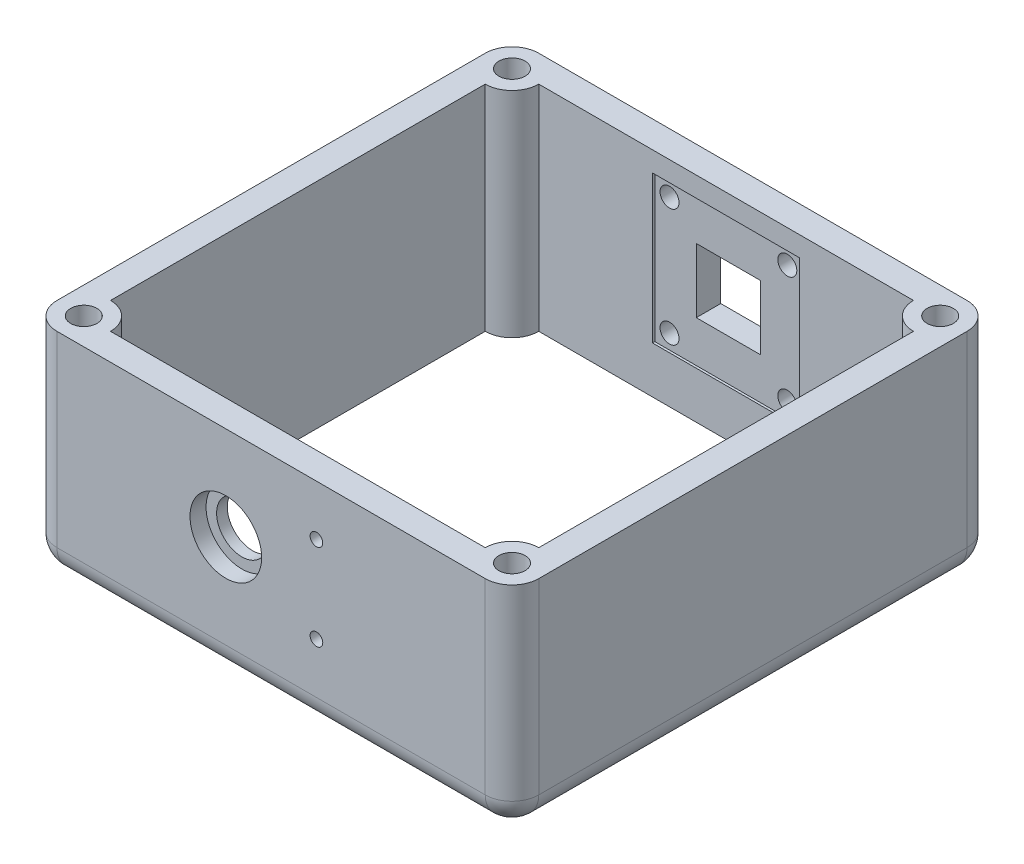
SolidWorks part; units mm, degrees
note: '?' marks a value the reader was unsure of. The reader was unsure of these and kept them because the rebuilt part matched: shared geometry of "Sketch5<3>", "Sketch13<4>", "Sketch13<5>", "Sketch13<6>", "Sketch24<3>".
ref_plane "Front Plane" through (0, 0, 0) normal (0, 0, 1) x (1, 0, 0)
ref_plane "Top Plane" through (0, 0, 0) normal (0, 1, 0) x (1, 0, 0)
ref_plane "Right Plane" through (0, 0, 0) normal (1, 0, 0) x (0, 0, -1)
sketch "Sketch1" plane through (0, 0, 0) normal (0, 1, 0) x (1, 0, 0)
  line L1 (-57.15, 57.15) -> (57.15, 57.15)
  line L2 (-57.15, 57.15) -> (-57.15, -57.15)
  line L3 (-57.15, -57.15) -> (57.15, -57.15)
  line L4 (57.15, 57.15) -> (57.15, -57.15)
  point P4 (0, 57.15)
  point P7 (-57.15, 0)
  dimension "D1" = 114.3
  dimension "D2" = 114.3
extrude "Boss-Extrude1" add sketch "Sketch1" along normal mid plane 50.8
sketch "Sketch2" plane through (0, 25.4, 0) normal (0, 1, 0) x (1, 0, 0)
  line L1 (-50.8, 50.8) -> (50.8, 50.8)
  line L2 (-50.8, 50.8) -> (-50.8, -50.8)
  line L3 (-50.8, -50.8) -> (50.8, -50.8)
  line L4 (50.8, 50.8) -> (50.8, -50.8)
  arc A0 (-50.8, 44.45) -> (-44.45, 50.8) centre (-50.8, 50.8) ccw
  arc A1 (44.45, 50.8) -> (50.8, 44.45) centre (50.8, 50.8) ccw
  arc A2 (-50.8, -44.45) -> (-44.45, -50.8) centre (-50.8, -50.8) cw
  arc A3 (44.45, -50.8) -> (50.8, -44.45) centre (50.8, -50.8) cw
  point P4 (0, 50.8)
  point P5 (50.8, 0)
  dimension "D3" = 6.35
  dimension "D4" = 6.35
  dimension "D5" = 6.35
  dimension "D6" = 6.35
  dimension "D1" = 101.6
  dimension "D2" = 101.6
extrude "Cut-Extrude1" cut sketch "Sketch2" against normal blind 50.8 contours L3 A3 L4 A1 L1 A0 L2 A2
hole_wizard "CBORE for #0 Binding Head Machine Screw1" positions "3DSketch2" profile "Sketch4" counterbore size "#0" standard "ANSI Inch"
sketch3d "3DSketch2"
  point P0 (-50.8, 25.4, -50.8)
  point P3 (50.8, 25.4, -50.8)
  point P6 (-50.8, 25.4, 50.8)
  point P9 (50.8, 25.4, 50.8)
sketch "Sketch4" plane through (-50.8, 25.4, -50.8) normal (1, 0, 0) x (0, 0, 1)
  line L0 (0, 0) -> (0, 18.288)
  line L1 (0, 18.288) -> (0.9271, 17.7309)
  line L2 (0.9271, 17.7309) -> (0.9271, 9.144)
  line L3 (0.9271, 9.144) -> (3.1115, 9.144)
  line L4 (3.1115, 9.144) -> (3.1115, 0)
  line L5 (3.1115, 0) -> (0, 0)
  line L10 (0, 18.288) -> (-0.9271, 17.7309) construction
  line L11 (0, -6.35) -> (0, 107.95) construction
  dimension "Hole Dia." = 1.8542
  dimension "Hole Depth" = 18.288
  dimension "C'Bore Dia." = 6.223
  dimension "C'Bore Depth" = 9.144
  dimension "Drill Angle" = 118
sketch "Sketch5" plane through (0, 0, -50.8) normal (0, 0, 1) x (1, 0, 0)
  line L0 (7.625, 3.175) -> (-7.625, 3.175) construction
  line L1 (-17.47, 20.645) -> (17.47, 20.645)
  line L2 (-17.47, 20.645) -> (-17.47, -14.295)
  line L3 (-17.47, -14.295) -> (17.47, -14.295)
  line L4 (17.47, 20.645) -> (17.47, -14.295)
  line L5 (-7.625, 10.8) -> (7.625, 10.8)
  line L6 (-7.625, 10.8) -> (-7.625, -4.45)
  line L7 (-7.625, -4.45) -> (7.625, -4.45)
  line L8 (7.625, 10.8) -> (7.625, -4.45)
  line L10 (-57.15, 25.4) -> (-57.15, -25.4) construction
  line L11 (0, 10.8) -> (0, -4.45) construction
  line L12 (-57.15, 25.4) -> (57.15, 25.4) construction
  point P8 (0, 10.8)
  point P9 (0, 20.645)
  point P12 (17.47, 3.175)
  point P13 (7.625, 3.175)
  dimension "D1" = 34.94
  dimension "D2" = 15.25
  dimension "D3" = 15.25
  dimension "D4" = 34.94
  dimension "D5" = 39.68
  dimension "D6" = 4.755
extrude "Cut-Extrude5" cut sketch "Sketch5" against normal blind 0.55
extrude "Cut-Extrude6" cut sketch "Sketch5<3>" against normal up to next
sketch "Sketch5<3>" plane through (0, 0, -50.8) normal (0, 0, 1) x (1, 0, 0) same geometry as "Sketch5"
sketch "Sketch13" plane through (0, 0, -57.15) normal (0, 0, -1) x (-1, 0, 0)
  line L0 (-57.15, 25.4) -> (57.15, 25.4) construction
  line L1 (-57.15, 25.4) -> (-57.15, -25.4) construction
  line L2 (57.15, 25.4) -> (57.15, -25.4) construction
  line L3 (-14.2875, -0.635) -> (-14.2875, -5.715) construction
  line L4 (14.2875, -5.715) -> (14.2875, -0.635) construction
  line L5 (13.7875, 0.602) -> (13.7875, -6.952)
  line L6 (14.7875, 0.602) -> (14.7875, -6.952)
  line L7 (11.5934, -5.8691) -> (16.9816, -0.4809)
  line L8 (11.5934, -0.4809) -> (16.9816, -5.8691)
  circle A0 centre (-14.2875, -3.175) radius 2.54
  circle A1 centre (14.2875, -3.175) radius 2.54
  circle A2 centre (14.2875, -3.175) radius 3.81
  point P19 (13.7875, -3.175)
  point P20 (14.7875, -3.175)
  dimension "D1" = 5.08
  dimension "D2" = 5.08
  dimension "D7" = 7.62
  dimension "D3" = 28.575
  dimension "D4" = 28.575
  dimension "D5" = 42.8625
  dimension "D6" = 42.8625
  dimension "D8" = 1
  dimension "D9" = 0.5
  dimension "D10" = 45
  dimension "D11" = 45
extrude "Boss-Extrude2" add sketch "Sketch13" along normal blind 1.27 contours A0
ref_plane "Plane1" through (14.2875, -3.175, -57.15) normal (0, -1, 0) x (-1, 0, 0)
sketch "Sketch14" plane through (14.2875, -3.175, -57.15) normal (0, -1, 0) x (-1, 0, 0)
  line L0 (0, 1.27) -> (0, 2.54)
  line L1 (2.54, 1.27) -> (-2.54, 1.27) construction
  line L2 (0, 2.54) -> (2.286, 2.54)
  line L3 (2.286, 2.54) -> (2.64, 1.905)
  line L4 (2.64, 1.905) -> (2.64, 1.27)
  line L5 (2.64, 1.27) -> (2.54, 1.27)
  line L6 (2.54, 0) -> (2.54, 1.27) construction
  line L7 (2.54, 1.27) -> (0, 1.27)
  dimension "D1" = 1.27
  dimension "D2" = 0.1
  dimension "D3" = 2.286
  dimension "D4" = 0.635
revolve "Revolve1" add sketch "Sketch14" angle 360 about L0
ref_plane "Plane2" through (-14.2875, -3.175, -57.15) normal (0, -1, 0) x (-1, 0, 0)
extrude "Cut-Extrude7" cut sketch "Sketch13<4>" against normal blind 2.54 contours L8 A1 L7 L6 | L6 A1 L8 | L5 A1 L6 L8 L7 | L7 A1 L6 | L6 A1 L5 L8 L7 | L7 L8 L6 | L8 L5 L7 | L8 A1 L7 L5 | L7 A1 L5 | L5 A1 L8
sketch "Sketch13<4>" plane through (0, 0, -57.15) normal (0, 0, -1) x (-1, 0, 0) same geometry as "Sketch13"
extrude "Cut-Extrude8" cut sketch "Sketch13<5>" against normal blind 0.635 contours L7 A2 L5 A1 | L6 A2 L8 A1 | L7 A2 L6 A1 | L5 A2 L8 A1
sketch "Sketch13<5>" plane through (0, 0, -57.15) normal (0, 0, -1) x (-1, 0, 0) same geometry as "Sketch13"
extrude "Cut-Extrude9" cut sketch "Sketch13<6>" against normal blind 1.27 contours L6 A2 L5 A1 | L5 A2 L6 A1
sketch "Sketch13<6>" plane through (0, 0, -57.15) normal (0, 0, -1) x (-1, 0, 0) same geometry as "Sketch13"
sketch "Sketch17" plane through (-14.2875, -3.175, -57.15) normal (0, -1, 0) x (-1, 0, 0)
  line L0 (0, -1.27) -> (0, -2.54)
  line L1 (0.5, -1.27) -> (-0.5, -1.27) construction
  line L2 (0, -2.54) -> (2.286, -2.54)
  line L3 (2.286, -2.54) -> (2.64, -1.905)
  line L7 (2.54, -1.27) -> (0, -1.27)
  line L8 (2.64, -1.905) -> (2.64, -1.27)
  line L9 (2.64, -1.27) -> (2.54, -1.27)
  dimension "D1" = 2.54
  dimension "D2" = 2.286
  dimension "D3" = 0.1
  dimension "D4" = 1.27
  dimension "D5" = 0.635
revolve "Cut-Revolve1" cut sketch "Sketch17" angle 360 about L0
ref_plane "Plane3" through (0, 3.175, 0) normal (0, -1, 0) x (0, 0, 1)
ref_axis "Axis1" through (0, 3.175, 62.865) along (0, 0, -1)?
ref_axis "Axis2" through (0, 59.3725, 0) along (0, -1, 0)?
sketch "Sketch20" plane through (0, 0, -57.15) normal (0, 0, -1) x (-1, 0, 0)
  line L1 (-13.97, 17.145) -> (13.97, 17.145)
  line L2 (-13.97, 17.145) -> (-13.97, -10.795)
  line L3 (-13.97, -10.795) -> (13.97, -10.795)
  line L4 (13.97, 17.145) -> (13.97, -10.795)
  point P4 (0, 17.145)
  point P9 (13.97, 3.175)
  dimension "D1" = 27.94
  dimension "D2" = 27.94
hole_wizard "CBORE for M5 Hex Head Bolt2" positions "3DSketch4" profile "Sketch21" counterbore size "M5" standard "ANSI Metric"
sketch3d "3DSketch4"
  point P0 (13.97, 17.145, -57.15)
  point P3 (-13.97, 17.145, -57.15)
  point P6 (-13.97, -10.795, -57.15)
  point P9 (13.97, -10.795, -57.15)
sketch "Sketch21" plane through (13.97, 17.145, -57.15) normal (1, 0, 0) x (0, 1, 0)
  line L0 (0, 0) -> (0, 18.288)
  line L1 (0, 18.288) -> (2.75, 16.6356)
  line L2 (2.75, 16.6356) -> (2.75, 5.8)
  line L3 (2.75, 5.8) -> (2.25, 5.8)
  line L4 (2.25, 5.8) -> (2.25, 0)
  line L5 (2.25, 0) -> (0, 0)
  line L10 (0, 18.288) -> (-2.75, 16.6356) construction
  line L11 (0, -6.35) -> (0, 107.95) construction
  dimension "Hole Dia." = 5.5
  dimension "Hole Depth" = 18.288
  dimension "C'Bore Dia." = 4.5
  dimension "C'Bore Depth" = 5.8
  dimension "Drill Angle" = 118
sketch "Sketch23" plane through (0, 0, -59.69) normal (0, 0, -1) x (-1, 0, 0)
  line L0 (-14.7875, -0.5828) -> (-14.7875, -5.7672)
  line L1 (-13.7875, -0.5828) -> (-13.7875, -5.7672)
  line L2 (-14.2875, -0.535) -> (-14.2875, -5.815) construction
  circle A0 centre (-14.2875, -3.175) radius 2.64 construction
  circle A1 centre (-14.2875, -3.175) radius 2.64
  circle M1 centre (-14.2875, -3.175) radius 2.286
  dimension "D1" = 5.28
  dimension "D2" = 0.5
  dimension "D3" = 0.5
extrude "Cut-Extrude10" cut sketch "Sketch23" against normal blind 2.032 contours L2 L0 M1 | L2 L1 M1 | L2 A1 L0 M1 | A1 L2 L1 M1 | L2 A1 L1 M1 | L2 L0 A1 M1
pattern_circular "CirPattern1" count 4 every 90 about axis through (0, 3.175, 0) along (0, 0, 1) of "Boss-Extrude2", "Revolve1", "Cut-Extrude7", "Cut-Extrude8", "Cut-Extrude9", "Cut-Revolve1", "Cut-Extrude10"
ref_plane "Plane4" through (0, 3.175, 0) normal (0, -1, 0) x (-1, 0, 0)
ref_axis "Axis3" through (-62.865, 3.175, 0) along (1, 0, 0)?
fillet "Fillet1" radius 6.35 8 edges at (0, -25.4, -57.15) (57.15, -25.4, 0) (0, -25.4, 57.15) (-57.15, -25.4, 0) (-57.15, 0, 57.15) (-57.15, 0, -57.15) (57.15, 0, 57.15) (57.15, 0, -57.15)
sketch "Sketch24" plane through (0, 0, 57.15) normal (0, 0, 1) x (1, 0, 0)
  line L0 (-62.865, 3.175) -> (62.865, 3.175) construction
  line L1 (-10.75, 3.175) -> (10.75, 3.175) construction
  line L2 (10.75, -7.075) -> (10.75, 13.425)
  line L3 (10.75, 3.175) -> (15.75, 3.175)
  circle A0 centre (-10.75, 3.175) radius 8.5
  circle A1 centre (-10.75, 3.175) radius 6
  circle A2 centre (10.75, 13.425) radius 1.5
  circle A3 centre (10.75, -7.075) radius 1.5
  point P5 (0, 3.175)
  point P11 (10.75, 3.175)
  dimension "D1" = 12
  dimension "D2" = 17
  dimension "D5" = 3
  dimension "D6" = 3
  dimension "D3" = 21.5
  dimension "D4" = 20.5
  dimension "D7" = 5
extrude "Cut-Extrude11" cut sketch "Sketch24" against normal blind 3.81
extrude "Cut-Extrude12" cut sketch "Sketch24<3>" against normal up to next
sketch "Sketch24<3>" plane through (0, 0, 57.15) normal (0, 0, 1) x (1, 0, 0) same geometry as "Sketch24"
sketch "Sketch25" plane through (0, 0, 50.8) normal (0, 0, -1) x (-1, 0, 0)
  line L0 (-15.75, -2.775) -> (-15.75, 9.125)
  line L1 (-10.75, 3.175) -> (-15.75, 3.175) construction
  line L2 (-17.2103, 11.6305) -> (-17.2103, 6.6195)
  line L3 (-14.2897, 11.6305) -> (-14.2897, 6.6195)
  line L4 (-17.2103, -0.2695) -> (-17.2103, -5.2805)
  line L5 (-14.2897, -0.2695) -> (-14.2897, -5.2805)
  circle A0 centre (-15.75, 9.125) radius 2.9
  circle A1 centre (-15.75, -2.775) radius 2.9
  point P4 (-15.75, 3.175)
  dimension "D1" = 5.8
  dimension "D2" = 5.8
  dimension "D3" = 11.9
  dimension "D4" = 5.011
  dimension "D5" = 5.011
extrude "Boss-Extrude3" add sketch "Sketch25" along normal blind 2.8
